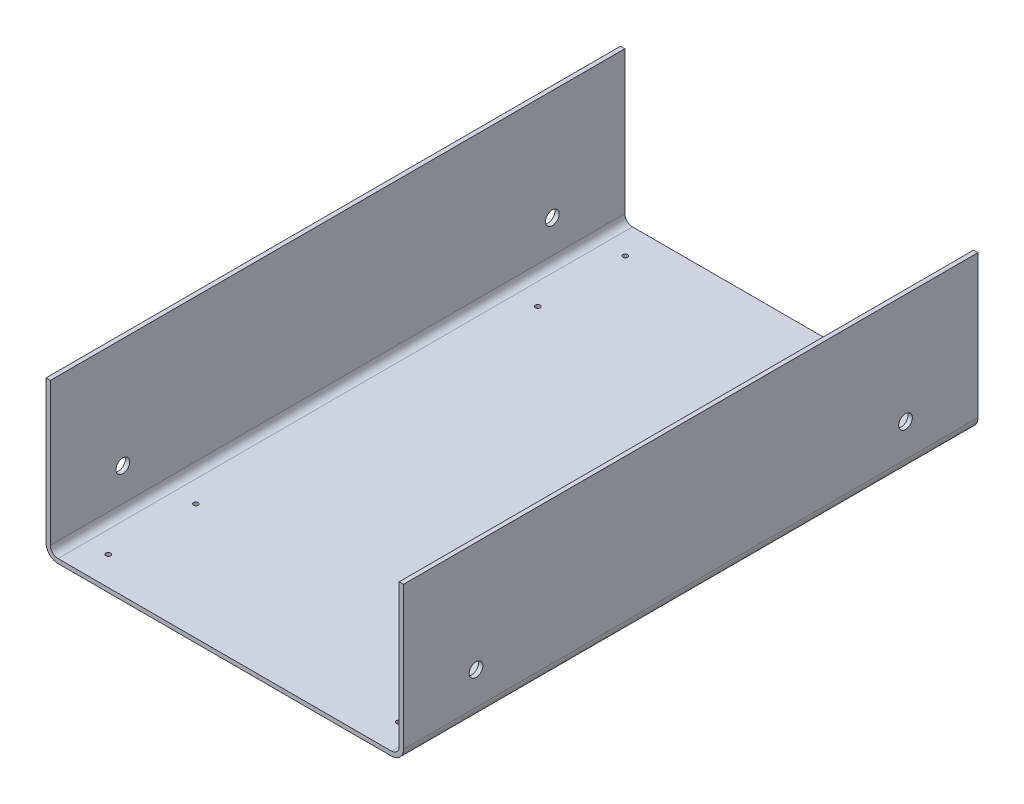
SolidWorks part; units mm, degrees
material "5052-H32"
ref_plane "Front Plane" through (0, 0, 0) normal (0, 0, 1) x (1, 0, 0)
ref_plane "Top Plane" through (0, 0, 0) normal (0, 1, 0) x (1, 0, 0)
ref_plane "Right Plane" through (0, 0, 0) normal (1, 0, 0) x (0, 0, -1)
sketch "Sketch1" plane through (0, 0, 0) normal (0, 0, 1) x (1, 0, 0)
  line L8 (127.5, 110) -> (127.5, 0)
  line L9 (-127.5, 0) -> (127.5, 0)
  line L10 (-127.5, 0) -> (-127.5, 110)
  line L11 (130.68, 110) -> (130.68, -3.18)
  line L12 (-130.68, -3.18) -> (130.68, -3.18)
  line L13 (-130.68, -3.18) -> (-130.68, 110)
  line L14 (127.5, 110) -> (130.68, 110)
  line L15 (-127.5, 110) -> (-130.68, 110)
  point P5 (0, 0)
  dimension "D1" = 255
  dimension "D2" = 110
  dimension "D3" = 3.18
extrude "Boss-Extrude1" add sketch "Sketch1" along normal blind 420
fillet "Inside Fillet" radius 5.56 2 edges at (127.5, 0, 210) (-127.5, 0, 210)
fillet "Outside Fillet" radius 8.73 2 edges at (-130.68, -3.18, 210) (130.68, -3.18, 210)
sketch "Sketch2" plane through (130.68, 0, 0) normal (1, 0, 0) x (0, 0, -1)
  line L0 (-420, 5.55) -> (-420, 110) construction
  line L2 (0, 5.55) -> (0, 110) construction
  line L4 (-367, 29.5) -> (-367, 0) construction
  line L7 (-53, 29.5) -> (-53, 0) construction
  circle A0 centre (-367, 29.5) radius 5
  circle A1 centre (-53, 29.5) radius 5
  dimension "D3" = 10
  dimension "D4" = 10
  dimension "D1" = 53
  dimension "D2" = 29.5
  dimension "D5" = 53
  dimension "D6" = 29.5
extrude "Bearing Holes" cut sketch "Sketch2" against normal up to surface (261.36 mm away) up to face at (-130.68, 57.775, 210)
sketch "Sketch3" plane through (0, 0, 0) normal (0, 1, 0) x (1, 0, 0)
  line L0 (-106.15, -335) -> (-106.15, -399) construction
  line L1 (121.94, -420) -> (-121.94, -420) construction
  line L2 (-127.5, -420) -> (-127.5, 0) construction
  line L3 (-130.68, -210) -> (130.68, -210) construction
  line L4 (-130.68, -420) -> (-130.68, 0) construction
  line L5 (130.68, -420) -> (130.68, 0) construction
  line L6 (0, -420) -> (0, -210) construction
  line L7 (-106.15, -85) -> (-106.15, -21) construction
  line L8 (121.94, 0) -> (-121.94, 0) construction
  line L9 (106.15, -335) -> (106.15, -399) construction
  line L10 (106.15, -85) -> (106.15, -21) construction
  circle A0 centre (-106.15, -335) radius 1.7526
  circle A1 centre (-106.15, -399) radius 1.7526
  circle A6 centre (106.15, -399) radius 1.7526
  circle A7 centre (106.15, -335) radius 1.7526
  circle A8 centre (-106.15, -85) radius 1.7526
  circle A9 centre (-106.15, -21) radius 1.7526
  circle A10 centre (106.15, -21) radius 1.7526
  circle A11 centre (106.15, -85) radius 1.7526
  point P4 (-106.15, -367)
  point P23 (-106.15, -53)
  dimension "D4" = 3.5052
  dimension "D5" = 3.5052
  dimension "D6" = 3.5052
  dimension "D7" = 3.5052
  dimension "D1" = 64
  dimension "D2" = 53
  dimension "D3" = 21.35
  dimension "D8" = 64
  dimension "D9" = 21.35
  dimension "D10" = 53
extrude "Motor Mount Holes" cut sketch "Sketch3" against normal up to next
equation "\"W\"= 255mm"
equation "\"L\"= 420mm"
equation "\"Offset\"= 16mm"
equation "\"H\"= 110mm"
equation "\"T\"= 4.7625 * 2 / 3mm"
equation "\"Inside Fillet Radius\"= 5.55625mm"
equation "\"Hole\"=25mm"
equation "\"D1@Boss-Extrude1\"=\"L\""
equation "\"Compartment Width1\"= 90mm"
equation "\"Compartment Width2\"= 90mm"
equation "\"D1@Sketch1\"=\"W\""
equation "\"D2@Sketch1\"=\"H\""
equation "\"D3@Sketch1\"=\"T\""
equation "\"D1@Inside Fillet\"=\"Inside Fillet Radius\""
equation "\"D1@Outside Fillet\"=\"Inside Fillet Radius\"+\"T\""
equation "\"D2@Sketch3\"=53"
